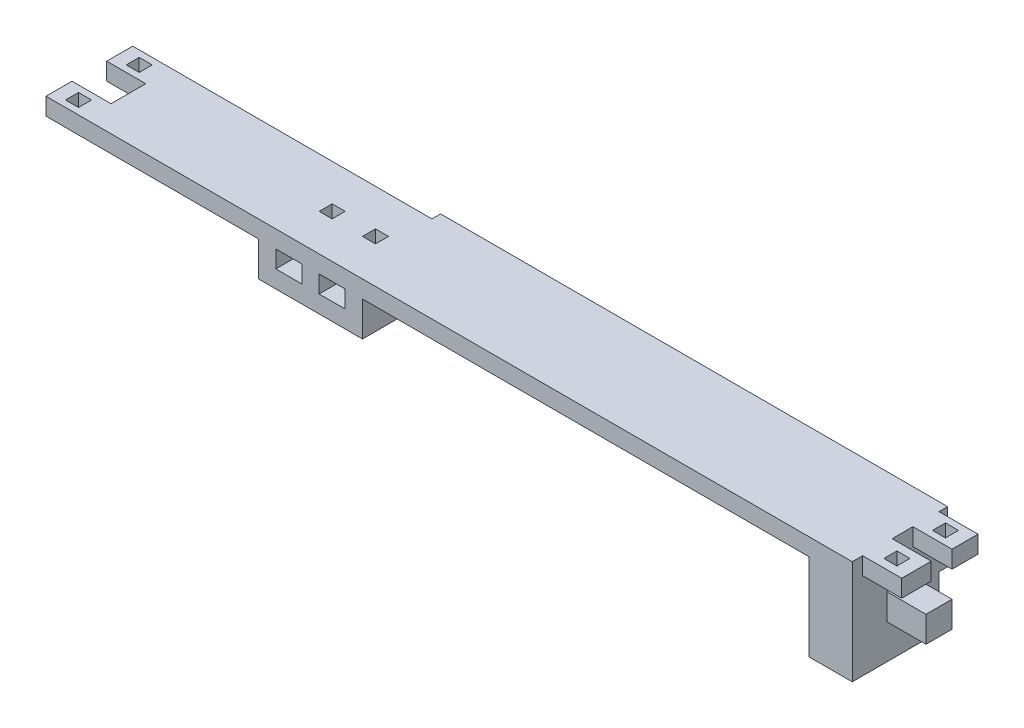
SolidWorks part; units mm, degrees
ref_plane "Front Plane" through (0, 0, 0) normal (0, 0, 1) x (1, 0, 0)
ref_plane "Top Plane" through (0, 0, 0) normal (0, 1, 0) x (1, 0, 0)
ref_plane "Right Plane" through (0, 0, 0) normal (1, 0, 0) x (0, 0, -1)
sketch "Sketch2" plane through (0, 0, 0) normal (0, 1, 0) x (1, 0, 0)
  line L1 (0, 0) -> (194.96, 0)
  line L2 (0, 0) -> (0, 6)
  line L3 (0, 6) -> (194.96, 6)
  line L4 (194.96, 0) -> (194.96, 6)
  dimension "D1" = 194.96
  dimension "D2" = 6
extrude "Boss-Extrude1" add sketch "Sketch2" along normal blind 4
sketch "Sketch3" plane through (0, 0, 0) normal (0, 0, -1) x (-1, 0, 0)
  line L0 (-194.96, 4) -> (0, 4) construction
  line L1 (-9, 4) -> (-185.96, 4)
  line L2 (-9, 4) -> (-9, 0)
  line L3 (-9, 0) -> (-185.96, 0)
  line L4 (-185.96, 4) -> (-185.96, 0)
  line L5 (-194.96, 0) -> (0, 0) construction
  line L7 (-194.96, 4) -> (-194.96, 0) construction
  line L8 (0, 4) -> (0, 0) construction
  dimension "D1" = 9
  dimension "D2" = 9
extrude "Boss-Extrude2" add sketch "Sketch3" against normal blind 14
sketch "Sketch4" plane through (9, 0, 0) normal (-1, 0, 0) x (0, 0, 1)
  line L0 (14, 0) -> (0, 0) construction
  line L1 (14, 4) -> (8, 4)
  line L2 (14, 4) -> (14, 0)
  line L3 (14, 0) -> (8, 0)
  line L4 (8, 4) -> (8, 0)
  line L6 (0, 0) -> (0, 4) construction
  dimension "D1" = 6
extrude "Boss-Extrude3" add sketch "Sketch4" along normal blind 9
sketch "Sketch5" plane through (185.96, 0, 0) normal (1, 0, 0) x (0, 0, -1)
  line L0 (-14, 4) -> (0, 4) construction
  line L1 (-11.6, 4) -> (-4.8, 4)
  line L2 (-11.6, 4) -> (-11.6, 0)
  line L3 (-11.6, 0) -> (-4.8, 0)
  line L4 (-4.8, 4) -> (-4.8, 0)
  line L5 (-14, 0) -> (0, 0) construction
  line L6 (-14, 4) -> (-14, 0) construction
  line L7 (0, 4) -> (0, 0) construction
  dimension "D1" = 2.4
  dimension "D2" = 4.8
extrude "Boss-Extrude4" add sketch "Sketch5" along normal blind 9
sketch "Sketch6" plane through (0, 4, 0) normal (0, 1, 0) x (1, 0, 0)
  line L0 (0, 6) -> (0, 0) construction
  line L1 (3, 4.5) -> (6, 4.5)
  line L2 (3, 4.5) -> (3, 1.5)
  line L3 (3, 1.5) -> (6, 1.5)
  line L4 (6, 4.5) -> (6, 1.5)
  line L5 (194.96, 6) -> (0, 6) construction
  line L7 (0, -14) -> (185.96, -14) construction
  line L8 (3, -9.5) -> (6, -9.5)
  line L9 (3, -9.5) -> (3, -12.5)
  line L10 (3, -12.5) -> (6, -12.5)
  line L11 (6, -9.5) -> (6, -12.5)
  line L12 (0, -14) -> (0, -8) construction
  line L13 (194.96, 0) -> (194.96, 6) construction
  line L14 (188.96, 4.5) -> (191.96, 4.5)
  line L15 (188.96, 4.5) -> (188.96, 1.5)
  line L16 (188.96, 1.5) -> (191.96, 1.5)
  line L17 (191.96, 4.5) -> (191.96, 1.5)
  line L18 (194.96, -4.8) -> (194.96, -11.6) construction
  line L19 (191.96, -6.7) -> (188.96, -6.7)
  line L20 (191.96, -6.7) -> (191.96, -9.7)
  line L21 (191.96, -9.7) -> (188.96, -9.7)
  line L22 (188.96, -6.7) -> (188.96, -9.7)
  line L23 (194.96, -4.8) -> (185.96, -4.8) construction
  dimension "D1" = 3
  dimension "D2" = 3
  dimension "D3" = 3
  dimension "D4" = 1.5
  dimension "D5" = 3
  dimension "D6" = 1.5
  dimension "D7" = 3
  dimension "D8" = 1.5
  dimension "D9" = 3
  dimension "D10" = 3
  dimension "D11" = 3
  dimension "D12" = 3
  dimension "D13" = 3
  dimension "D14" = 3
  dimension "D15" = 1.9
extrude "Cut-Extrude1" cut sketch "Sketch6" against normal up to next
sketch "Sketch7" plane through (0, 0, 0) normal (0, -1, 0) x (1, 0, 0)
  line L0 (194.96, -6) -> (0, -6) construction
  line L1 (185.96, 14) -> (175.96, 14)
  line L2 (185.96, 14) -> (185.96, -6)
  line L3 (185.96, -6) -> (175.96, -6)
  line L4 (175.96, 14) -> (175.96, -6)
  dimension "D1" = 10
extrude "Boss-Extrude5" add sketch "Sketch7" along normal blind 20
sketch "Sketch8" plane through (0, 0, 0) normal (0, -1, 0) x (1, 0, 0)
  line L0 (175.96, -6) -> (0, -6) construction
  line L1 (49, -6) -> (185.96, -6)
  line L2 (49, -6) -> (49, 0)
  line L3 (49, 0) -> (185.96, 0)
  line L4 (185.96, -6) -> (185.96, 0)
  line L5 (185.96, -6) -> (185.96, 14) construction
  line L6 (9, 8) -> (9, 0) construction
  dimension "D1" = 40
  dimension "D2" = 6
extrude "Boss-Extrude6" add sketch "Sketch8" along normal blind 8
chamfer "Chamfer1" distance 12 angle 50 1 edges at (175.96, -8, -3) first distance on face at (175.96, -9.3333, 2.6667)
sketch "Sketch9" plane through (0, 0, 0) normal (0, 0, 1) x (1, 0, 0)
  line L0 (175.96, 0) -> (0, 0) construction
  line L1 (49, -8) -> (55, -8)
  line L2 (49, -8) -> (49, 0)
  line L3 (49, 0) -> (55, 0)
  line L5 (161.659, -8) -> (49, -8) construction
  line L6 (61, -8) -> (73, -8)
  line L8 (61, 0) -> (73, 0)
  line L9 (73, -8) -> (73, 0)
  line L10 (175.96, 0) -> (49, 0) construction
  line L11 (55, 0) -> (61, 0)
  line L12 (55, -8) -> (61, -8)
  dimension "D1" = 24
extrude "Boss-Extrude7" add sketch "Sketch9" along normal up to surface (14 mm away) up to face at (120.64, -5.3333, 14)
sketch "Sketch10" plane through (0, 0, 14) normal (0, 0, 1) x (1, 0, 0)
  line L0 (49, 0) -> (0, 0) construction
  line L1 (53, 0) -> (59, 0)
  line L2 (53, 0) -> (53, -4)
  line L3 (53, -4) -> (59, -4)
  line L4 (59, 0) -> (59, -4)
  line L5 (49, 0) -> (49, -8) construction
  line L6 (0, 4) -> (185.96, 4) construction
  line L7 (63, 0) -> (69, 0)
  line L8 (63, 0) -> (63, -4)
  line L9 (63, -4) -> (69, -4)
  line L10 (69, 0) -> (69, -4)
  dimension "D1" = 6
  dimension "D2" = 4
  dimension "D3" = 0
  dimension "D4" = 4
  dimension "D5" = 6
  dimension "D6" = 4
extrude "Cut-Extrude2" cut sketch "Sketch10" against normal up to next
sketch "Sketch11" plane through (0, 4, 0) normal (0, 1, 0) x (1, 0, 0)
  line L0 (53, 6) -> (53, -14) construction
  line L1 (54.5, -2.5) -> (57.5, -2.5)
  line L2 (54.5, -2.5) -> (54.5, -5.5)
  line L3 (54.5, -5.5) -> (57.5, -5.5)
  line L4 (57.5, -2.5) -> (57.5, -5.5)
  line L5 (0, -14) -> (185.96, -14) construction
  line L8 (63, 6) -> (63, -14) construction
  line L9 (64.5, -5.5) -> (67.5, -5.5)
  line L10 (64.5, -5.5) -> (64.5, -2.5)
  line L11 (64.5, -2.5) -> (67.5, -2.5)
  line L12 (67.5, -5.5) -> (67.5, -2.5)
  dimension "D1" = 1.5
  dimension "D2" = 3
  dimension "D3" = 3
  dimension "D4" = 8.5
  dimension "D5" = 3
  dimension "D6" = 3
  dimension "D7" = 1.5
  dimension "D8" = 8.5
extrude "Cut-Extrude3" cut sketch "Sketch11" against normal up to next
sketch "Sketch12" plane through (0, 0, -6) normal (0, 0, -1) x (-1, 0, 0)
  line L0 (-194.96, 4) -> (0, 4) construction
  line L1 (-185.96, 4) -> (-69, 4)
  line L2 (-185.96, 4) -> (-185.96, -8)
  line L3 (-185.96, -8) -> (-69, -8)
  line L4 (-69, 4) -> (-69, -8)
  line L5 (-49, -8) -> (-161.659, -8) construction
  line L6 (-185.96, -20) -> (-185.96, 0) construction
  line L7 (-69, 0) -> (-69, -4) construction
  dimension "D1" = 0
  dimension "D2" = 0
extrude "Boss-Extrude8" add sketch "Sketch12" along normal blind 2
sketch "Sketch13" plane through (185.96, 0, 0) normal (1, 0, 0) x (0, 0, -1)
  line L0 (-4.8, 0) -> (-11.6, 0) construction
  line L1 (-6, -6) -> (0, -6)
  line L2 (-6, -6) -> (-6, -12)
  line L3 (-6, -12) -> (0, -12)
  line L4 (0, -6) -> (0, -12)
  line L5 (-14, 4) -> (-14, -20) construction
  line L8 (-11.6, 4) -> (-11.6, 0) construction
  line L9 (6, 4) -> (6, 0) construction
  line L10 (-11.6, 4) -> (-11.6, 0) construction
  dimension "D1" = 6
  dimension "D2" = 6
  dimension "D3" = 6
  dimension "D4" = 8
extrude "Boss-Extrude9" add sketch "Sketch13" along normal blind 9
